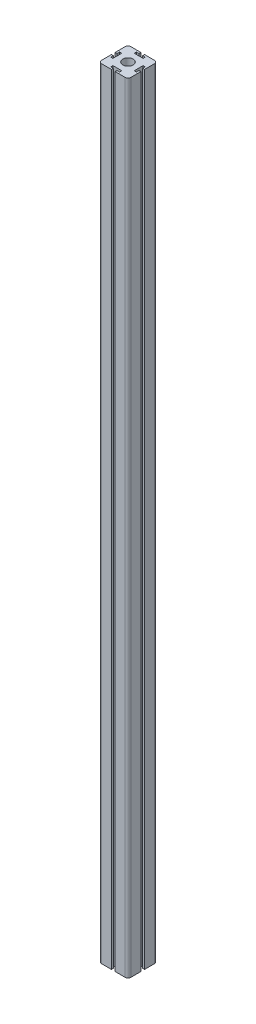
SolidWorks part; units mm, degrees
ref_plane "Front Plane" through (0, 0, 0) normal (0, 0, 1) x (1, 0, 0)
ref_plane "Top Plane" through (0, 0, 0) normal (0, 1, 0) x (1, 0, 0)
ref_plane "Right Plane" through (0, 0, 0) normal (1, 0, 0) x (0, 0, -1)
sketch "Sketch2" plane through (0, 0, 0) normal (0, 1, 0) x (1, 0, 0)
  line L0 (-20, 0) -> (0, 0) construction
  line L1 (-16, -20) -> (16, -20)
  line L2 (-20, -16) -> (-20, 16)
  line L3 (-16, 20) -> (16, 20)
  line L4 (20, -16) -> (20, 16)
  line L5 (-20, -20) -> (20, 20) construction
  line L6 (-20, 20) -> (20, -20) construction
  arc A0 (-20, 16) -> (-16, 20) centre (-16, 16) cw
  arc A1 (16, 20) -> (20, 16) centre (16, 16) cw
  arc A2 (16, -20) -> (20, -16) centre (16, -16) ccw
  arc A3 (-16, -20) -> (-20, -16) centre (-16, -16) cw
  circle A4 centre (0, 0) radius 7
  point P0 (0, 0)
  dimension "D2" = 4
  dimension "D3" = 14
  dimension "D1" = 40
extrude "Extrude1" add sketch "Sketch2" against normal blind 1059
sketch "Sketch3" plane through (0, 0, 0) normal (0, 1, 0) x (1, 0, 0)
  line L0 (-2.5, 20) -> (-2.5, 17.5)
  line L1 (16, 20) -> (-16, 20) construction
  line L2 (-2.5, 17.5) -> (-6, 17.5)
  line L3 (-6, 17.5) -> (-6, 14.5)
  line L4 (-6, 14.5) -> (6, 14.5)
  line L5 (6, 14.5) -> (6, 17.5)
  line L6 (6, 17.5) -> (2.5, 17.5)
  line L7 (2.5, 17.5) -> (2.5, 20)
  line L8 (2.5, 20) -> (-2.5, 20)
  line L9 (0, 0) -> (0, 20) construction
  point P13 (0, 14.5)
  dimension "D1" = 2.5
  dimension "D2" = 3
  dimension "D3" = 12
  dimension "D4" = 5
extrude "Extrude2" cut sketch "Sketch3" against normal through all
ref_axis "Axis1" through (0, 3.5, 0) along (0, -1, 0)
pattern_circular "CirPattern1" count 4 over 360 about axis through (0, 3.5, 0) along (0, -1, 0) of "Extrude2"
